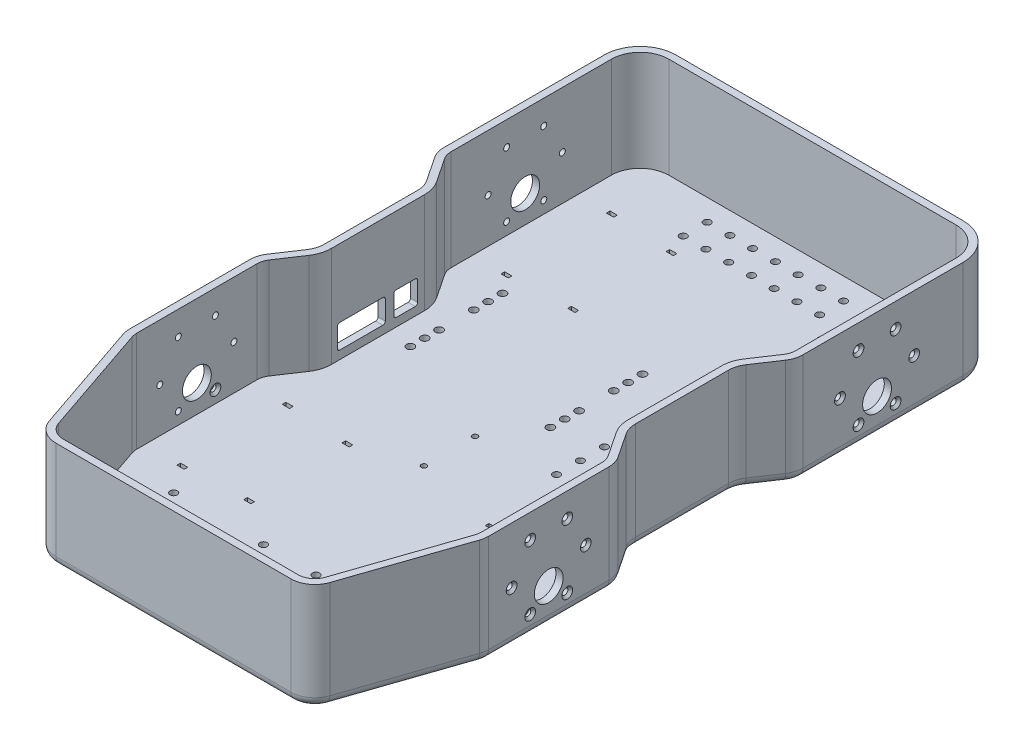
SolidWorks part; units mm, degrees
note: The reader was unsure of these and kept them because the rebuilt part matched: shared geometry of "Sketch13<7>", "Sketch13<15>", "Sketch13<16>".
ref_plane "Front Plane" through (0, 0, 0) normal (0, 0, 1) x (1, 0, 0)
ref_plane "Top Plane" through (0, 0, 0) normal (0, 1, 0) x (1, 0, 0)
ref_plane "Right Plane" through (0, 0, 0) normal (1, 0, 0) x (0, 0, -1)
sketch "Sketch1" plane through (0, 0, 0) normal (0, 1, 0) x (1, 0, 0)
  line L0 (-74.4651, -71.569) -> (-58.5591, -118.2267)
  line L3 (-49.094, -125) -> (49.094, -125)
  line L5 (-73.3205, -12.4808) -> (-66.6795, -2.5192)
  line L6 (-65, 3.0278) -> (-65, 41.9722)
  line L7 (-66.6795, 47.5192) -> (-73.3205, 57.4808)
  line L9 (0, 0) -> (0, 199.7745) construction
  line L10 (74.4651, -71.569) -> (58.5591, -118.2267)
  line L11 (73.3205, -12.4808) -> (66.6795, -2.5192)
  line L12 (65, 3.0278) -> (65, 41.9722)
  line L13 (66.6795, 47.5192) -> (73.3205, 57.4808)
  line L15 (75, -18.0278) -> (75, -68.3423)
  line L16 (-75, -18.0278) -> (-75, -68.3423)
  line L21 (75, 63.0278) -> (75, 130)
  line L22 (60, 145) -> (-60, 145)
  line L23 (-75, 130) -> (-75, 63.0278)
  arc A1 (74.4651, -71.569) -> (75, -68.3423) centre (65, -68.3423) ccw
  arc A2 (58.5591, -118.2267) -> (49.094, -125) centre (49.094, -115) cw
  arc A3 (-49.094, -125) -> (-58.5591, -118.2267) centre (-49.094, -115) cw
  arc A4 (-74.4651, -71.569) -> (-75, -68.3423) centre (-65, -68.3423) cw
  arc A6 (-66.6795, -2.5192) -> (-65, 3.0278) centre (-75, 3.0278) ccw
  arc A7 (-65, 41.9722) -> (-66.6795, 47.5192) centre (-75, 41.9722) ccw
  arc A8 (75, -18.0278) -> (73.3205, -12.4808) centre (65, -18.0278) ccw
  arc A9 (66.6795, -2.5192) -> (65, 3.0278) centre (75, 3.0278) cw
  arc A10 (66.6795, 47.5192) -> (65, 41.9722) centre (75, 41.9722) ccw
  arc A11 (75, 63.0278) -> (73.3205, 57.4808) centre (65, 63.0278) cw
  arc A12 (-73.3205, 57.4808) -> (-75, 63.0278) centre (-65, 63.0278) cw
  arc A13 (-75, 130) -> (-60, 145) centre (-60, 130) cw
  arc A14 (75, 130) -> (60, 145) centre (60, 130) ccw
  arc A15 (-75, -18.0278) -> (-73.3205, -12.4808) centre (-65, -18.0278) cw
  point P24 (75, -70)
  point P27 (56.25, -125)
  point P30 (-56.25, -125)
  point P33 (-75, -70)
  point P36 (-75, -15)
  point P39 (-65, 0)
  point P42 (-65, 45)
  point P45 (75, -15)
  point P48 (65, 0)
  point P51 (65, 45)
  point P54 (75, 70)
  point P57 (-75, 70)
  dimension "D8" = 10
  dimension "D9" = 15
  dimension "D11" = 15
  dimension "D14" = 10
  dimension "D2" = 55
  dimension "D5" = 85
  dimension "D13" = 18.75
  dimension "D16" = 55
  dimension "D3" = 270
  dimension "D4" = 75
  dimension "D6" = 150
  dimension "D7" = 65
extrude "Boss-Extrude1" add sketch "Sketch1" along normal blind 45
shell "Shell1" thickness 3
sketch "Sketch13" plane through (-75, 0, 0) normal (-1, 0, 0) x (0, 0, 1)
  line L0 (35.435, 34.9234) -> (43.185, 21.5) construction
  line L1 (43.185, 21.5) -> (27.685, 21.5) construction
  line L2 (43.185, 21.5) -> (35.435, 8.0766) construction
  line L3 (43.185, 21.5) -> (43.185, 14.4801) construction
  line L4 (18.0278, 0) -> (68.3423, 0)
  line L5 (68.3423, 0) -> (68.3423, 45)
  line L6 (68.3423, 45) -> (18.0278, 45)
  line L7 (18.0278, 45) -> (18.0278, 0)
  line L8 (18.0278, 0) -> (68.3423, 0)
  line L9 (68.3423, 0) -> (68.3423, 45)
  line L10 (68.3423, 45) -> (18.0278, 45)
  line L12 (-18.2522, 98.402) -> (-18.2522, -4.5228) construction
  line L13 (-94, 21.5) -> (-109.5, 21.5) construction
  line L14 (-94, 21.5) -> (-101.75, 8.0766) construction
  line L15 (-101.75, 34.9234) -> (-94, 21.5) construction
  line L16 (-94, 21.5) -> (-94, 14.4801) construction
  line L17 (-94, 21.5) -> (43.185, 21.5) construction
  line L18 (-130, 45) -> (-63.0278, 45) construction
  line L19 (-130, 45) -> (-130, 0) construction
  line L26 (18.0278, 45) -> (18.0278, 0)
  arc A0 (52.185, 8.0803) -> (52.185, 8.075) centre (50.935, 8.0766) cw
  arc A1 (52.185, 8.075) -> (52.185, 8.0803) centre (50.935, 8.0766) cw
  arc A2 (59.935, 21.5037) -> (59.935, 21.4983) centre (58.685, 21.5) cw
  arc A3 (59.935, 21.4983) -> (59.935, 21.5037) centre (58.685, 21.5) cw
  arc A4 (29.274, 33.6957) -> (30.3513, 8.1754) centre (43.185, 21.5) ccw
  arc A5 (30.3513, 8.1754) -> (29.274, 33.6957) centre (43.185, 21.5) ccw
  arc A6 (52.185, 34.9271) -> (52.185, 34.9217) centre (50.935, 34.9234) cw
  arc A7 (52.185, 34.9217) -> (52.185, 34.9271) centre (50.935, 34.9234) cw
  arc A8 (37.3975, 12.8118) -> (37.3802, 16.0874) centre (43.185, 14.4801) ccw
  arc A9 (37.3802, 16.0874) -> (37.3975, 12.8118) centre (43.185, 14.4801) ccw
  arc A12 (34.185, 8.075) -> (34.185, 8.0803) centre (35.435, 8.0766) ccw
  arc A13 (34.185, 8.0803) -> (34.185, 8.075) centre (35.435, 8.0766) ccw
  arc A28 (34.185, 34.9217) -> (34.185, 34.9271) centre (35.435, 34.9234) ccw
  arc A29 (34.185, 34.9271) -> (34.185, 34.9217) centre (35.435, 34.9234) ccw
  arc A32 (26.435, 21.4983) -> (26.435, 21.5037) centre (27.685, 21.5) ccw
  arc A33 (26.435, 21.5037) -> (26.435, 21.4983) centre (27.685, 21.5) ccw
  arc A37 (-100.5, 34.9234) -> (-100.5, 34.9234) centre (-101.75, 34.9234) ccw
  arc A38 (-82.5393, 6.9775) -> (-83.333, 36.615) centre (-94, 21.5) ccw
  arc A40 (-88.6695, 11.6757) -> (-88.6761, 17.2971) centre (-94, 14.4801) ccw
  arc A41 (-108.25, 21.5) -> (-108.25, 21.5) centre (-109.5, 21.5) ccw
  arc A44 (-108.25, 21.5) -> (-108.25, 21.5) centre (-109.5, 21.5) ccw
  arc A45 (-100.5, 34.9234) -> (-100.5, 34.9234) centre (-101.75, 34.9234) ccw construction
  arc A46 (-100.5, 8.0766) -> (-100.5, 8.0766) centre (-101.75, 8.0766) ccw
  arc A47 (-83.333, 36.615) -> (-82.5393, 6.9775) centre (-94, 21.5) ccw
  arc A48 (-88.6761, 17.2971) -> (-88.6695, 11.6757) centre (-94, 14.4801) ccw
  arc A49 (-100.5, 8.0766) -> (-100.5, 8.0766) centre (-101.75, 8.0766) ccw
  arc A50 (-87.5, 8.0766) -> (-87.5, 8.0766) centre (-86.25, 8.0766) cw
  arc A51 (-87.5, 8.0766) -> (-87.5, 8.0766) centre (-86.25, 8.0766) cw
  arc A52 (-79.75, 21.5) -> (-79.75, 21.5) centre (-78.5, 21.5) cw
  arc A53 (-79.75, 21.5) -> (-79.75, 21.5) centre (-78.5, 21.5) cw
  arc A54 (-87.5, 34.9234) -> (-87.5, 34.9234) centre (-86.25, 34.9234) cw
  arc A55 (-87.5, 34.9234) -> (-87.5, 34.9234) centre (-86.25, 34.9234) cw
  circle A56 centre (-101.75, 34.9234) radius 1.25
  circle A57 centre (-86.25, 34.9234) radius 1.25
  circle A58 centre (-78.5, 21.5) radius 1.25
  circle A59 centre (-86.25, 8.0766) radius 1.25
  circle A60 centre (-101.75, 8.0766) radius 1.25
  circle A61 centre (-109.5, 21.5) radius 1.25
  dimension "D11" = 18.5
  dimension "D12" = 6.0232
  dimension "D14" = 1.25
  dimension "D15" = 1.25
  dimension "D16" = 1.25
  dimension "D23" = 18.5
  dimension "D25" = 6.0232
  dimension "D28" = 1.25
  dimension "D30" = 1.25
  dimension "D31" = 1.25
  dimension "D2" = 21.5
  dimension "D3" = 60
  dimension "D4" = 60
  dimension "D5" = 30
  dimension "D6" = 15.5
  dimension "D8" = 15.5
  dimension "D7" = 15.5
  dimension "D13" = 7.0199
  dimension "D17" = 15.5
  dimension "D18" = 60
  dimension "D19" = 15.5
  dimension "D20" = 60
  dimension "D21" = 30
  dimension "D22" = 7.0199
  dimension "D29" = 15.5
  dimension "D9" = 50.3145
  dimension "D10" = 25.1573
  dimension "D24" = 66.9722
  dimension "D26" = 36
extrude "Cut-Extrude1" cut sketch "Sketch13" against normal blind 200 and the other way blind 10 contours A8 A9
extrude "Cut-Extrude2" cut sketch "Sketch13<7>" against normal blind 200 and the other way blind 10 contours A28 A29 | A32 A33 | A12 A13 | A1 A0 | A3 A2 | A7 A6
sketch "Sketch13<7>" plane through (-75, 0, 0) normal (-1, 0, 0) x (0, 0, 1) same geometry as "Sketch13"
chamfer "Chamfer1" distance 1 angle 45 1 edges at (-75, 34.9234, 34.185)
chamfer "Chamfer2" distance 1 angle 45 5 edges at (-72, 8.0766, 34.185) (-75, 8.0766, 49.685) (-75, 21.5, 57.435) (-75, 34.9234, 49.685) (-75, 21.5, 26.435)
chamfer "Chamfer3" distance 1 angle 45 1 edges at (-75, 8.0766, 34.185)
chamfer "Chamfer4" distance 1 angle 45 7 edges at (75, 8.0766, 52.185) (72, 8.0766, 52.185) (75, 8.0766, 36.685) (75, 21.5, 28.935) (75, 34.9234, 36.685) (75, 21.5, 59.935) (75, 34.9234, 52.185)
extrude "Cut-Extrude11" cut sketch "Sketch13<15>" against normal through all contours A59 | A60 | A56 | A61 | A57 | A58
sketch "Sketch13<15>" plane through (-75, 0, 0) normal (-1, 0, 0) x (0, 0, 1) same geometry as "Sketch13"
chamfer "Chamfer5" distance 1 angle 45 12 edges at (75, 34.9234, -100.5) (75, 21.5, -108.25) (75, 8.0766, -100.5) (75, 8.0766, -85) (75, 21.5, -77.25) (75, 34.9234, -85) (-75, 8.0766, -100.5) (-75, 8.0766, -85) (-75, 21.5, -77.25) (-75, 21.5, -108.25) (-75, 34.9234, -100.5) (-75, 34.9234, -85)
extrude "Cut-Extrude12" cut sketch "Sketch13<16>" against normal through all contours A40 A48
sketch "Sketch13<16>" plane through (-75, 0, 0) normal (-1, 0, 0) x (0, 0, 1) same geometry as "Sketch13"
fillet "Fillet1" radius 4 28 edges at (70.6066, 0, -140.6066) (75, 0, -96.5139) (74.5709, 0, -60.1299) (70, 0, -52.5) (65.4291, 0, -44.8701) (65, 0, -22.5) (65.4291, 0, -0.1299) (70, 0, 7.5) (74.5709, 0, 15.1299) (75, 0, 43.185) (74.8654, 0, 69.9777) (66.5121, 0, 94.8979) (54.9134, 0, 123.1323) (0, 0, 125) (-54.9134, 0, 123.1323) (-66.5121, 0, 94.8979) (-74.8654, 0, 69.9777) (-75, 0, 43.185) (-74.5709, 0, 15.1299) (-70, 0, 7.5) (-65.4291, 0, -0.1299) (-65, 0, -22.5) (-65.4291, 0, -44.8701) (-70, 0, -52.5) (-74.5709, 0, -60.1299) (-75, 0, -96.5139) (-70.6066, 0, -140.6066) (0, 0, -145)
sketch "Sketch14" plane through (0, 3, 0) normal (0, 1, 0) x (1, 0, 0)
  line L14 (-72, 130) -> (-72, 63.0278)
  line L15 (-70.8244, 59.1449) -> (-64.1833, 49.1833)
  line L16 (-62, 41.9722) -> (-62, 3.0278)
  line L17 (-64.1833, -4.1833) -> (-70.8244, -14.1449)
  line L18 (-72, -18.0278) -> (-72, -68.3423)
  line L19 (-71.6256, -70.601) -> (-55.7195, -117.2587)
  line L20 (-49.094, -122) -> (49.094, -122)
  line L21 (55.7195, -117.2587) -> (71.6256, -70.601)
  line L22 (72, -68.3423) -> (72, -18.0278)
  line L23 (70.8244, -14.1449) -> (64.1833, -4.1833)
  line L24 (62, 3.0278) -> (62, 41.9722)
  line L25 (64.1833, 49.1833) -> (70.8244, 59.1449)
  line L26 (72, 63.0278) -> (72, 130)
  line L27 (60, 142) -> (-60, 142)
  line L28 (-72, 130) -> (-72, 63.0278)
  line L29 (-70.8244, 59.1449) -> (-64.1833, 49.1833)
  line L30 (-62, 41.9722) -> (-62, 3.0278)
  line L31 (-64.1833, -4.1833) -> (-70.8244, -14.1449)
  line L32 (-72, -18.0278) -> (-72, -68.3423)
  line L33 (-71.6256, -70.601) -> (-55.7195, -117.2587)
  line L34 (-49.094, -122) -> (49.094, -122)
  line L35 (55.7195, -117.2587) -> (71.6256, -70.601)
  line L36 (72, -68.3423) -> (72, -18.0278)
  line L37 (70.8244, -14.1449) -> (64.1833, -4.1833)
  line L38 (62, 3.0278) -> (62, 41.9722)
  line L39 (64.1833, 49.1833) -> (70.8244, 59.1449)
  line L40 (72, 63.0278) -> (72, 130)
  line L41 (60, 142) -> (-60, 142)
  arc A14 (-60, 142) -> (-72, 130) centre (-60, 130) ccw
  arc A15 (-72, 63.0278) -> (-70.8244, 59.1449) centre (-65, 63.0278) ccw
  arc A16 (-62, 41.9722) -> (-64.1833, 49.1833) centre (-75, 41.9722) ccw
  arc A17 (-64.1833, -4.1833) -> (-62, 3.0278) centre (-75, 3.0278) ccw
  arc A18 (-70.8244, -14.1449) -> (-72, -18.0278) centre (-65, -18.0278) ccw
  arc A19 (-72, -68.3423) -> (-71.6256, -70.601) centre (-65, -68.3423) ccw
  arc A20 (-55.7195, -117.2587) -> (-49.094, -122) centre (-49.094, -115) ccw
  arc A21 (49.094, -122) -> (55.7195, -117.2587) centre (49.094, -115) ccw
  arc A22 (71.6256, -70.601) -> (72, -68.3423) centre (65, -68.3423) ccw
  arc A23 (72, -18.0278) -> (70.8244, -14.1449) centre (65, -18.0278) ccw
  arc A24 (62, 3.0278) -> (64.1833, -4.1833) centre (75, 3.0278) ccw
  arc A25 (64.1833, 49.1833) -> (62, 41.9722) centre (75, 41.9722) ccw
  arc A26 (70.8244, 59.1449) -> (72, 63.0278) centre (65, 63.0278) ccw
  arc A27 (72, 130) -> (60, 142) centre (60, 130) ccw
  arc A28 (-60, 142) -> (-72, 130) centre (-60, 130) ccw
  arc A29 (-72, 63.0278) -> (-70.8244, 59.1449) centre (-65, 63.0278) ccw
  arc A30 (-62, 41.9722) -> (-64.1833, 49.1833) centre (-75, 41.9722) ccw
  arc A31 (-64.1833, -4.1833) -> (-62, 3.0278) centre (-75, 3.0278) ccw
  arc A32 (-70.8244, -14.1449) -> (-72, -18.0278) centre (-65, -18.0278) ccw
  arc A33 (-72, -68.3423) -> (-71.6256, -70.601) centre (-65, -68.3423) ccw
  arc A34 (-55.7195, -117.2587) -> (-49.094, -122) centre (-49.094, -115) ccw
  arc A35 (49.094, -122) -> (55.7195, -117.2587) centre (49.094, -115) ccw
  arc A36 (71.6256, -70.601) -> (72, -68.3423) centre (65, -68.3423) ccw
  arc A37 (72, -18.0278) -> (70.8244, -14.1449) centre (65, -18.0278) ccw
  arc A38 (62, 3.0278) -> (64.1833, -4.1833) centre (75, 3.0278) ccw
  arc A39 (64.1833, 49.1833) -> (62, 41.9722) centre (75, 41.9722) ccw
  arc A40 (70.8244, 59.1449) -> (72, 63.0278) centre (65, 63.0278) ccw
  arc A41 (72, 130) -> (60, 142) centre (60, 130) ccw
  dimension "D1" = 0
sketch "Sketch15" plane through (0, 3, 0) normal (0, 1, 0) x (1, 0, 0)
  line L14 (-72, 130) -> (-72, 63.0278)
  line L15 (-70.8244, 59.1449) -> (-64.1833, 49.1833)
  line L16 (-62, 41.9722) -> (-62, 3.0278)
  line L17 (-64.1833, -4.1833) -> (-70.8244, -14.1449)
  line L18 (-72, -18.0278) -> (-72, -68.3423)
  line L19 (-71.6256, -70.601) -> (-55.7195, -117.2587)
  line L20 (-49.094, -122) -> (49.094, -122)
  line L21 (55.7195, -117.2587) -> (71.6256, -70.601)
  line L22 (72, -68.3423) -> (72, -18.0278)
  line L23 (70.8244, -14.1449) -> (64.1833, -4.1833)
  line L24 (62, 3.0278) -> (62, 41.9722)
  line L25 (64.1833, 49.1833) -> (70.8244, 59.1449)
  line L26 (72, 63.0278) -> (72, 130)
  line L27 (60, 142) -> (-60, 142)
  line L28 (-72, 130) -> (-72, 63.0278)
  line L29 (-70.8244, 59.1449) -> (-64.1833, 49.1833)
  line L30 (-62, 41.9722) -> (-62, 3.0278)
  line L31 (-64.1833, -4.1833) -> (-70.8244, -14.1449)
  line L32 (-72, -18.0278) -> (-72, -68.3423)
  line L33 (-71.6256, -70.601) -> (-55.7195, -117.2587)
  line L34 (-49.094, -122) -> (49.094, -122)
  line L35 (55.7195, -117.2587) -> (71.6256, -70.601)
  line L36 (72, -68.3423) -> (72, -18.0278)
  line L37 (70.8244, -14.1449) -> (64.1833, -4.1833)
  line L38 (62, 3.0278) -> (62, 41.9722)
  line L39 (64.1833, 49.1833) -> (70.8244, 59.1449)
  line L40 (72, 63.0278) -> (72, 130)
  line L41 (60, 142) -> (-60, 142)
  arc A14 (-60, 142) -> (-72, 130) centre (-60, 130) ccw
  arc A15 (-72, 63.0278) -> (-70.8244, 59.1449) centre (-65, 63.0278) ccw
  arc A16 (-62, 41.9722) -> (-64.1833, 49.1833) centre (-75, 41.9722) ccw
  arc A17 (-64.1833, -4.1833) -> (-62, 3.0278) centre (-75, 3.0278) ccw
  arc A18 (-70.8244, -14.1449) -> (-72, -18.0278) centre (-65, -18.0278) ccw
  arc A19 (-72, -68.3423) -> (-71.6256, -70.601) centre (-65, -68.3423) ccw
  arc A20 (-55.7195, -117.2587) -> (-49.094, -122) centre (-49.094, -115) ccw
  arc A21 (49.094, -122) -> (55.7195, -117.2587) centre (49.094, -115) ccw
  arc A22 (71.6256, -70.601) -> (72, -68.3423) centre (65, -68.3423) ccw
  arc A23 (72, -18.0278) -> (70.8244, -14.1449) centre (65, -18.0278) ccw
  arc A24 (62, 3.0278) -> (64.1833, -4.1833) centre (75, 3.0278) ccw
  arc A25 (64.1833, 49.1833) -> (62, 41.9722) centre (75, 41.9722) ccw
  arc A26 (70.8244, 59.1449) -> (72, 63.0278) centre (65, 63.0278) ccw
  arc A27 (72, 130) -> (60, 142) centre (60, 130) ccw
  arc A28 (-60, 142) -> (-72, 130) centre (-60, 130) ccw
  arc A29 (-72, 63.0278) -> (-70.8244, 59.1449) centre (-65, 63.0278) ccw
  arc A30 (-62, 41.9722) -> (-64.1833, 49.1833) centre (-75, 41.9722) ccw
  arc A31 (-64.1833, -4.1833) -> (-62, 3.0278) centre (-75, 3.0278) ccw
  arc A32 (-70.8244, -14.1449) -> (-72, -18.0278) centre (-65, -18.0278) ccw
  arc A33 (-72, -68.3423) -> (-71.6256, -70.601) centre (-65, -68.3423) ccw
  arc A34 (-55.7195, -117.2587) -> (-49.094, -122) centre (-49.094, -115) ccw
  arc A35 (49.094, -122) -> (55.7195, -117.2587) centre (49.094, -115) ccw
  arc A36 (71.6256, -70.601) -> (72, -68.3423) centre (65, -68.3423) ccw
  arc A37 (72, -18.0278) -> (70.8244, -14.1449) centre (65, -18.0278) ccw
  arc A38 (62, 3.0278) -> (64.1833, -4.1833) centre (75, 3.0278) ccw
  arc A39 (64.1833, 49.1833) -> (62, 41.9722) centre (75, 41.9722) ccw
  arc A40 (70.8244, 59.1449) -> (72, 63.0278) centre (65, 63.0278) ccw
  arc A41 (72, 130) -> (60, 142) centre (60, 130) ccw
  dimension "D1" = 0
sketch "Sketch16" plane through (0, 0, 0) normal (0, -1, 0) x (1, 0, 0)
  line L14 (-60, -141) -> (60, -141)
  line L15 (71, -130) -> (71, -63.0278)
  line L16 (69.9923, -59.6996) -> (63.3513, -49.738)
  line L17 (61, -41.9722) -> (61, -3.0278)
  line L18 (63.3513, 4.738) -> (69.9923, 14.6996)
  line L19 (71, 18.0278) -> (71, 68.3423)
  line L20 (70.6791, 70.2783) -> (54.773, 116.936)
  line L21 (49.094, 121) -> (-49.094, 121)
  line L22 (-54.773, 116.936) -> (-70.6791, 70.2783)
  line L23 (-71, 68.3423) -> (-71, 18.0278)
  line L24 (-69.9923, 14.6996) -> (-63.3513, 4.738)
  line L25 (-61, -3.0278) -> (-61, -41.9722)
  line L26 (-63.3513, -49.738) -> (-69.9923, -59.6996)
  line L27 (-71, -63.0278) -> (-71, -130)
  line L28 (-60, -141) -> (60, -141)
  line L29 (71, -130) -> (71, -63.0278)
  line L30 (69.9923, -59.6996) -> (63.3513, -49.738)
  line L31 (61, -41.9722) -> (61, -3.0278)
  line L32 (63.3513, 4.738) -> (69.9923, 14.6996)
  line L33 (71, 18.0278) -> (71, 68.3423)
  line L34 (70.6791, 70.2783) -> (54.773, 116.936)
  line L35 (49.094, 121) -> (-49.094, 121)
  line L36 (-54.773, 116.936) -> (-70.6791, 70.2783)
  line L37 (-71, 68.3423) -> (-71, 18.0278)
  line L38 (-69.9923, 14.6996) -> (-63.3513, 4.738)
  line L39 (-61, -3.0278) -> (-61, -41.9722)
  line L40 (-63.3513, -49.738) -> (-69.9923, -59.6996)
  line L41 (-71, -63.0278) -> (-71, -130)
  arc A14 (60, -141) -> (71, -130) centre (60, -130) ccw
  arc A15 (71, -63.0278) -> (69.9923, -59.6996) centre (65, -63.0278) ccw
  arc A16 (61, -41.9722) -> (63.3513, -49.738) centre (75, -41.9722) ccw
  arc A17 (63.3513, 4.738) -> (61, -3.0278) centre (75, -3.0278) ccw
  arc A18 (69.9923, 14.6996) -> (71, 18.0278) centre (65, 18.0278) ccw
  arc A19 (71, 68.3423) -> (70.6791, 70.2783) centre (65, 68.3423) ccw
  arc A20 (54.773, 116.936) -> (49.094, 121) centre (49.094, 115) ccw
  arc A21 (-49.094, 121) -> (-54.773, 116.936) centre (-49.094, 115) ccw
  arc A22 (-70.6791, 70.2783) -> (-71, 68.3423) centre (-65, 68.3423) ccw
  arc A23 (-71, 18.0278) -> (-69.9923, 14.6996) centre (-65, 18.0278) ccw
  arc A24 (-61, -3.0278) -> (-63.3513, 4.738) centre (-75, -3.0278) ccw
  arc A25 (-63.3513, -49.738) -> (-61, -41.9722) centre (-75, -41.9722) ccw
  arc A26 (-69.9923, -59.6996) -> (-71, -63.0278) centre (-65, -63.0278) ccw
  arc A27 (-71, -130) -> (-60, -141) centre (-60, -130) ccw
  arc A28 (60, -141) -> (71, -130) centre (60, -130) ccw
  arc A29 (71, -63.0278) -> (69.9923, -59.6996) centre (65, -63.0278) ccw
  arc A30 (61, -41.9722) -> (63.3513, -49.738) centre (75, -41.9722) ccw
  arc A31 (63.3513, 4.738) -> (61, -3.0278) centre (75, -3.0278) ccw
  arc A32 (69.9923, 14.6996) -> (71, 18.0278) centre (65, 18.0278) ccw
  arc A33 (71, 68.3423) -> (70.6791, 70.2783) centre (65, 68.3423) ccw
  arc A34 (54.773, 116.936) -> (49.094, 121) centre (49.094, 115) ccw
  arc A35 (-49.094, 121) -> (-54.773, 116.936) centre (-49.094, 115) ccw
  arc A36 (-70.6791, 70.2783) -> (-71, 68.3423) centre (-65, 68.3423) ccw
  arc A37 (-71, 18.0278) -> (-69.9923, 14.6996) centre (-65, 18.0278) ccw
  arc A38 (-61, -3.0278) -> (-63.3513, 4.738) centre (-75, -3.0278) ccw
  arc A39 (-63.3513, -49.738) -> (-61, -41.9722) centre (-75, -41.9722) ccw
  arc A40 (-69.9923, -59.6996) -> (-71, -63.0278) centre (-65, -63.0278) ccw
  arc A41 (-71, -130) -> (-60, -141) centre (-60, -130) ccw
  dimension "D1" = 0
sketch "Sketch18" plane through (0, 3, 0) normal (0, 1, 0) x (1, 0, 0)
  line L0 (-72, -68.3423) -> (72, -68.3423) construction
  line L1 (0, -68.3423) -> (0, -58.9421) construction
  line L14 (-72, 130) -> (-72, 63.0278)
  line L15 (-70.8244, 59.1449) -> (-64.1833, 49.1833)
  line L16 (-62, 41.9722) -> (-62, 3.0278)
  line L17 (-64.1833, -4.1833) -> (-70.8244, -14.1449)
  line L18 (-72, -18.0278) -> (-72, -68.3423)
  line L19 (-71.6256, -70.601) -> (-55.7195, -117.2587)
  line L20 (-49.094, -122) -> (49.094, -122)
  line L21 (55.7195, -117.2587) -> (71.6256, -70.601)
  line L22 (72, -68.3423) -> (72, -18.0278)
  line L23 (70.8244, -14.1449) -> (64.1833, -4.1833)
  line L24 (62, 3.0278) -> (62, 41.9722)
  line L25 (64.1833, 49.1833) -> (70.8244, 59.1449)
  line L26 (72, 63.0278) -> (72, 130)
  line L27 (60, 142) -> (-60, 142)
  line L28 (-72, 130) -> (-72, 63.0278)
  line L29 (-70.8244, 59.1449) -> (-64.1833, 49.1833)
  line L30 (-62, 41.9722) -> (-62, 3.0278)
  line L31 (-64.1833, -4.1833) -> (-70.8244, -14.1449)
  line L32 (-72, -18.0278) -> (-72, -68.3423)
  line L33 (-71.6256, -70.601) -> (-55.7195, -117.2587)
  line L34 (-49.094, -122) -> (49.094, -122)
  line L35 (55.7195, -117.2587) -> (71.6256, -70.601)
  line L36 (72, -68.3423) -> (72, -18.0278)
  line L37 (70.8244, -14.1449) -> (64.1833, -4.1833)
  line L38 (62, 3.0278) -> (62, 41.9722)
  line L39 (64.1833, 49.1833) -> (70.8244, 59.1449)
  line L40 (72, 63.0278) -> (72, 130)
  line L41 (60, 142) -> (-60, 142)
  arc A8 (-48.5, -112.3739) -> (-48.5, -115.3739) centre (-48.5, -113.8739) ccw
  arc A9 (-48.5, -115.3739) -> (-48.5, -112.3739) centre (-48.5, -113.8739) ccw
  arc A10 (-11, -112.3739) -> (-11, -115.3739) centre (-11, -113.8739) ccw
  arc A11 (-11, -115.3739) -> (-11, -112.3739) centre (-11, -113.8739) ccw
  arc A12 (-11, -77.8739) -> (-11, -74.8739) centre (-11, -76.3739) ccw
  arc A13 (-11, -74.8739) -> (-11, -77.8739) centre (-11, -76.3739) ccw
  arc A14 (-60, 142) -> (-72, 130) centre (-60, 130) ccw
  arc A15 (-72, 63.0278) -> (-70.8244, 59.1449) centre (-65, 63.0278) ccw
  arc A16 (-62, 41.9722) -> (-64.1833, 49.1833) centre (-75, 41.9722) ccw
  arc A17 (-64.1833, -4.1833) -> (-62, 3.0278) centre (-75, 3.0278) ccw
  arc A18 (-70.8244, -14.1449) -> (-72, -18.0278) centre (-65, -18.0278) ccw
  arc A19 (-72, -68.3423) -> (-71.6256, -70.601) centre (-65, -68.3423) ccw
  arc A20 (-55.7195, -117.2587) -> (-49.094, -122) centre (-49.094, -115) ccw
  arc A21 (49.094, -122) -> (55.7195, -117.2587) centre (49.094, -115) ccw
  arc A22 (71.6256, -70.601) -> (72, -68.3423) centre (65, -68.3423) ccw
  arc A23 (72, -18.0278) -> (70.8244, -14.1449) centre (65, -18.0278) ccw
  arc A24 (62, 3.0278) -> (64.1833, -4.1833) centre (75, 3.0278) ccw
  arc A25 (64.1833, 49.1833) -> (62, 41.9722) centre (75, 41.9722) ccw
  arc A26 (70.8244, 59.1449) -> (72, 63.0278) centre (65, 63.0278) ccw
  arc A27 (72, 130) -> (60, 142) centre (60, 130) ccw
  arc A28 (-60, 142) -> (-72, 130) centre (-60, 130) ccw
  arc A29 (-72, 63.0278) -> (-70.8244, 59.1449) centre (-65, 63.0278) ccw
  arc A30 (-62, 41.9722) -> (-64.1833, 49.1833) centre (-75, 41.9722) ccw
  arc A31 (-64.1833, -4.1833) -> (-62, 3.0278) centre (-75, 3.0278) ccw
  arc A32 (-70.8244, -14.1449) -> (-72, -18.0278) centre (-65, -18.0278) ccw
  arc A33 (-72, -68.3423) -> (-71.6256, -70.601) centre (-65, -68.3423) ccw
  arc A34 (-55.7195, -117.2587) -> (-49.094, -122) centre (-49.094, -115) ccw
  arc A35 (49.094, -122) -> (55.7195, -117.2587) centre (49.094, -115) ccw
  arc A36 (71.6256, -70.601) -> (72, -68.3423) centre (65, -68.3423) ccw
  arc A37 (72, -18.0278) -> (70.8244, -14.1449) centre (65, -18.0278) ccw
  arc A38 (62, 3.0278) -> (64.1833, -4.1833) centre (75, 3.0278) ccw
  arc A39 (64.1833, 49.1833) -> (62, 41.9722) centre (75, 41.9722) ccw
  arc A40 (70.8244, 59.1449) -> (72, 63.0278) centre (65, 63.0278) ccw
  arc A41 (72, 130) -> (60, 142) centre (60, 130) ccw
  arc A42 (-48.5, -74.8739) -> (-48.5, -77.8739) centre (-48.5, -76.3739) ccw
  arc A43 (-48.5, -77.8739) -> (-48.5, -74.8739) centre (-48.5, -76.3739) ccw
  arc A44 (48.5, -115.3739) -> (48.5, -112.3739) centre (48.5, -113.8739) cw
  arc A45 (48.5, -112.3739) -> (48.5, -115.3739) centre (48.5, -113.8739) cw
  arc A46 (11, -115.3739) -> (11, -112.3739) centre (11, -113.8739) cw
  arc A47 (11, -112.3739) -> (11, -115.3739) centre (11, -113.8739) cw
  arc A48 (11, -74.8739) -> (11, -77.8739) centre (11, -76.3739) cw
  arc A49 (11, -77.8739) -> (11, -74.8739) centre (11, -76.3739) cw
  arc A50 (48.5, -77.8739) -> (48.5, -74.8739) centre (48.5, -76.3739) cw
  arc A51 (48.5, -74.8739) -> (48.5, -77.8739) centre (48.5, -76.3739) cw
  dimension "D7" = 1.5
  dimension "D2" = 37.5
  dimension "D3" = 37.5
  dimension "D4" = 8.1261
  dimension "D5" = 37.5
  dimension "D6" = 61
  dimension "D1" = 0
extrude "Cut-Extrude5" cut sketch "Sketch18" against normal through all contours A49 A48 | A51 A50 | A42 A43 | A45 A44 | A47 A46 | A10 A11 | A8 A9 | A13 A12
sketch "Sketch19" plane through (0, 3, 0) normal (0, 1, 0) x (1, 0, 0)
  line L0 (62, 3.0278) -> (62, 41.9722) construction
  line L1 (60, 142) -> (-60, 142) construction
  circle A86 centre (56, -14.34) radius 1.125
  circle A88 centre (-5.98, -14.34) radius 1.125
  circle A90 centre (-5.98, 7) radius 1.125
  circle A92 centre (56, 7) radius 1.125
  dimension "D5" = 2.25
  dimension "D1" = 61.98
  dimension "D2" = 21.34
  dimension "D3" = 6
  dimension "D4" = 135
extrude "Cut-Extrude6" cut sketch "Sketch19" against normal through all contours A90 | A92 | A86 | A88
sketch "Sketch20" plane through (0, 3, 0) normal (0, 1, 0) x (1, 0, 0)
  line L14 (-72, 130) -> (-72, 63.0278)
  line L15 (-70.8244, 59.1449) -> (-64.1833, 49.1833)
  line L16 (-62, 41.9722) -> (-62, 3.0278)
  line L17 (-64.1833, -4.1833) -> (-70.8244, -14.1449)
  line L18 (-72, -18.0278) -> (-72, -68.3423)
  line L19 (-71.6256, -70.601) -> (-55.7195, -117.2587)
  line L20 (-49.094, -122) -> (49.094, -122)
  line L21 (55.7195, -117.2587) -> (71.6256, -70.601)
  line L22 (72, -68.3423) -> (72, -18.0278)
  line L23 (70.8244, -14.1449) -> (64.1833, -4.1833)
  line L24 (62, 3.0278) -> (62, 41.9722)
  line L25 (64.1833, 49.1833) -> (70.8244, 59.1449)
  line L26 (72, 63.0278) -> (72, 130)
  line L27 (60, 142) -> (-60, 142)
  line L28 (-72, 130) -> (-72, 63.0278)
  line L29 (-70.8244, 59.1449) -> (-64.1833, 49.1833)
  line L30 (-62, 41.9722) -> (-62, 3.0278)
  line L31 (-64.1833, -4.1833) -> (-70.8244, -14.1449)
  line L32 (-72, -18.0278) -> (-72, -68.3423)
  line L33 (-71.6256, -70.601) -> (-55.7195, -117.2587)
  line L34 (-49.094, -122) -> (49.094, -122)
  line L35 (55.7195, -117.2587) -> (71.6256, -70.601)
  line L36 (72, -68.3423) -> (72, -18.0278)
  line L37 (70.8244, -14.1449) -> (64.1833, -4.1833)
  line L38 (62, 3.0278) -> (62, 41.9722)
  line L39 (64.1833, 49.1833) -> (70.8244, 59.1449)
  line L40 (72, 63.0278) -> (72, 130)
  line L41 (60, 142) -> (-60, 142)
  arc A14 (-60, 142) -> (-72, 130) centre (-60, 130) ccw
  arc A15 (-72, 63.0278) -> (-70.8244, 59.1449) centre (-65, 63.0278) ccw
  arc A16 (-62, 41.9722) -> (-64.1833, 49.1833) centre (-75, 41.9722) ccw
  arc A17 (-64.1833, -4.1833) -> (-62, 3.0278) centre (-75, 3.0278) ccw
  arc A18 (-70.8244, -14.1449) -> (-72, -18.0278) centre (-65, -18.0278) ccw
  arc A19 (-72, -68.3423) -> (-71.6256, -70.601) centre (-65, -68.3423) ccw
  arc A20 (-55.7195, -117.2587) -> (-49.094, -122) centre (-49.094, -115) ccw
  arc A21 (49.094, -122) -> (55.7195, -117.2587) centre (49.094, -115) ccw
  arc A22 (71.6256, -70.601) -> (72, -68.3423) centre (65, -68.3423) ccw
  arc A23 (72, -18.0278) -> (70.8244, -14.1449) centre (65, -18.0278) ccw
  arc A24 (62, 3.0278) -> (64.1833, -4.1833) centre (75, 3.0278) ccw
  arc A25 (64.1833, 49.1833) -> (62, 41.9722) centre (75, 41.9722) ccw
  arc A26 (70.8244, 59.1449) -> (72, 63.0278) centre (65, 63.0278) ccw
  arc A27 (72, 130) -> (60, 142) centre (60, 130) ccw
  arc A28 (-60, 142) -> (-72, 130) centre (-60, 130) ccw
  arc A29 (-72, 63.0278) -> (-70.8244, 59.1449) centre (-65, 63.0278) ccw
  arc A30 (-62, 41.9722) -> (-64.1833, 49.1833) centre (-75, 41.9722) ccw
  arc A31 (-64.1833, -4.1833) -> (-62, 3.0278) centre (-75, 3.0278) ccw
  arc A32 (-70.8244, -14.1449) -> (-72, -18.0278) centre (-65, -18.0278) ccw
  arc A33 (-72, -68.3423) -> (-71.6256, -70.601) centre (-65, -68.3423) ccw
  arc A34 (-55.7195, -117.2587) -> (-49.094, -122) centre (-49.094, -115) ccw
  arc A35 (49.094, -122) -> (55.7195, -117.2587) centre (49.094, -115) ccw
  arc A36 (71.6256, -70.601) -> (72, -68.3423) centre (65, -68.3423) ccw
  arc A37 (72, -18.0278) -> (70.8244, -14.1449) centre (65, -18.0278) ccw
  arc A38 (62, 3.0278) -> (64.1833, -4.1833) centre (75, 3.0278) ccw
  arc A39 (64.1833, 49.1833) -> (62, 41.9722) centre (75, 41.9722) ccw
  arc A40 (70.8244, 59.1449) -> (72, 63.0278) centre (65, 63.0278) ccw
  arc A41 (72, 130) -> (60, 142) centre (60, 130) ccw
  arc A52 (6.2472, 24.4201) -> (6.7528, 24.4201) centre (6.5, 26) ccw
  arc A53 (6.7528, 24.4201) -> (6.2472, 24.4201) centre (6.5, 26) ccw
  arc A54 (6.2472, 50.9201) -> (6.7528, 50.9201) centre (6.5, 52.5) ccw
  arc A55 (6.7528, 50.9201) -> (6.2472, 50.9201) centre (6.5, 52.5) ccw
  arc A56 (-52.2528, 50.9201) -> (-51.7472, 50.9201) centre (-52, 52.5) ccw
  arc A57 (-51.7472, 50.9201) -> (-52.2528, 50.9201) centre (-52, 52.5) ccw
  arc A58 (-52.2528, 24.4201) -> (-51.7472, 24.4201) centre (-52, 26) ccw
  arc A59 (-51.7472, 24.4201) -> (-52.2528, 24.4201) centre (-52, 26) ccw
  dimension "D6" = 1.6
  dimension "D2" = 58.5
  dimension "D3" = 26.5
  dimension "D4" = 10
  dimension "D5" = 116
  dimension "D1" = 0
extrude "Cut-Extrude7" cut sketch "Sketch20" against normal blind 10 contours A56 A57 | A58 A59 | A54 A55 | A52 A53
sketch "Sketch21" plane through (0, 3, 0) normal (0, 1, 0) x (1, 0, 0)
  line L8 (60, 142) -> (-60, 142) construction
  line L9 (43.8703, 123.4984) -> (57, 123.4984)
  line L10 (43.8703, 123.4984) -> (43.8703, 132)
  line L11 (43.8703, 132) -> (57, 132)
  line L12 (57, 123.4984) -> (57, 132)
  line L13 (72, 63.0278) -> (72, 130) construction
  line L16 (32.0376, 116.2208) -> (32.0376, 114.1208)
  arc A10 (45.0376, 107.9708) -> (45.0876, 108.0208) centre (45.0376, 108.0208) ccw
  dimension "D1" = 13.1297
  dimension "D2" = 8.5016
  dimension "D3" = 10
  dimension "D4" = 15
extrude "Cut-Extrude13" cut sketch "Sketch21" against normal blind 10 contours L9 L12 L11 L10
ref_plane "Plane1" through (-192.3694, 44.6369, -11.8377) normal (0, 1, 0) x (1, 0, 0)
sketch "Sketch24" plane through (-192.3694, 44.6369, -11.8377) normal (0, 1, 0) x (1, 0, 0)
  line L0 (132.3696, 130.1623) -> (144.3693, 130.1623)
  line L1 (138.3694, 130.2075) -> (138.3694, 127.6134) construction
  line L2 (120.3694, 118.1623) -> (120.3694, 51.19) construction
  line L3 (252.3694, 130.1623) -> (132.3694, 130.1623) construction
  line L4 (192.3694, 130.1623) -> (192.3694, 114.7013) construction
  line L5 (252.3693, 130.1623) -> (240.3696, 130.1623)
  line L6 (130.3694, 17.1341) -> (130.3694, 5.1341)
  line L7 (130.3694, 11.1341) -> (133.3694, 11.1341) construction
  line L8 (143.2755, -133.8377) -> (241.4634, -133.8377) construction
  line L9 (130.3694, 30.245) -> (130.3694, -8.5559) construction
  line L10 (130.2722, 30.1341) -> (134.4415, 30.1341) construction
  line L11 (254.3694, 17.1341) -> (254.3694, 5.1341)
  line L12 (198.3226, -133.8377) -> (186.3226, -133.8377)
  line L15 (192.3226, -131.4888) -> (192.3226, -133.8377) construction
  arc A0 (132.3696, 130.1623) -> (144.3693, 130.1623) centre (138.3694, 130.2075) ccw
  circle A1 centre (138.3694, 127.1623) radius 1.5
  circle A2 centre (246.3694, 127.1623) radius 1.5
  arc A3 (252.3693, 130.1623) -> (240.3696, 130.1623) centre (246.3694, 130.2075) cw
  arc A5 (130.3694, 5.1341) -> (130.3694, 17.1341) centre (130.3694, 11.1341) ccw
  circle A6 centre (133.3694, 11.1341) radius 1.5
  circle A7 centre (251.3694, 11.1341) radius 1.5
  arc A8 (254.3694, 5.1341) -> (254.3694, 17.1341) centre (254.3694, 11.1341) cw
  arc A9 (198.3226, -133.8377) -> (186.3226, -133.8377) centre (192.3226, -133.8377) ccw
  circle A10 centre (192.3226, -131.4888) radius 1.5514
  dimension "D1" = 18
  dimension "D2" = 6
  dimension "D3" = 3
  dimension "D6" = 12
  dimension "D7" = 6
  dimension "D8" = 0
  dimension "D15" = 6
  dimension "D16" = 3.1027
  dimension "D4" = 3
  dimension "D5" = 0
  dimension "D9" = 38.8008
  dimension "D10" = 19
  dimension "D11" = 3
  dimension "D12" = 0
  dimension "D14" = 12
sketch "Sketch25" plane through (0, 3, 0) normal (0, 1, 0) x (1, 0, 0)
  line L0 (15.9476, 94) -> (10.8154, 94) construction
  line L1 (56.3327, 116.7507) -> (59.3327, 116.7507)
  line L2 (56.3327, 116.7507) -> (56.3327, 115.2507)
  line L3 (56.3327, 115.2507) -> (59.3327, 115.2507)
  line L4 (59.3327, 116.7507) -> (59.3327, 115.2507)
  line L5 (29.9219, 115.2967) -> (32.9219, 115.2967)
  line L6 (29.9219, 115.2967) -> (29.9219, 113.7967)
  line L7 (29.9219, 113.7967) -> (32.9219, 113.7967)
  line L8 (32.9219, 115.2967) -> (32.9219, 113.7967)
  line L9 (56.3327, 72.7493) -> (59.3327, 72.7493)
  line L10 (59.3327, 71.2493) -> (59.3327, 72.7493)
  line L11 (56.3327, 71.2493) -> (59.3327, 71.2493)
  line L12 (56.3327, 71.2493) -> (56.3327, 72.7493)
  line L13 (29.9219, 74.2033) -> (32.9219, 74.2033)
  line L14 (32.9219, 72.7033) -> (32.9219, 74.2033)
  line L15 (29.9219, 72.7033) -> (32.9219, 72.7033)
  line L16 (29.9219, 72.7033) -> (29.9219, 74.2033)
  line L17 (0, 128.6305) -> (0, 117.335) construction
  line L18 (-56.3327, 71.2493) -> (-56.3327, 72.7493)
  line L19 (-56.3327, 71.2493) -> (-59.3327, 71.2493)
  line L20 (-59.3327, 71.2493) -> (-59.3327, 72.7493)
  line L21 (-56.3327, 72.7493) -> (-59.3327, 72.7493)
  line L22 (-29.9219, 72.7033) -> (-29.9219, 74.2033)
  line L23 (-29.9219, 72.7033) -> (-32.9219, 72.7033)
  line L24 (-32.9219, 72.7033) -> (-32.9219, 74.2033)
  line L25 (-29.9219, 74.2033) -> (-32.9219, 74.2033)
  line L26 (-56.3327, 115.2507) -> (-59.3327, 115.2507)
  line L27 (-59.3327, 116.7507) -> (-59.3327, 115.2507)
  line L28 (-56.3327, 116.7507) -> (-59.3327, 116.7507)
  line L29 (-56.3327, 116.7507) -> (-56.3327, 115.2507)
  line L30 (-29.9219, 113.7967) -> (-32.9219, 113.7967)
  line L31 (-32.9219, 115.2967) -> (-32.9219, 113.7967)
  line L32 (-29.9219, 115.2967) -> (-32.9219, 115.2967)
  line L33 (-29.9219, 115.2967) -> (-29.9219, 113.7967)
  line L34 (28.4219, -21.6229) -> (31.4219, -21.6229)
  line L35 (54.8327, -20.1689) -> (54.8327, -21.6689)
  line L36 (31.4219, -64.2162) -> (31.4219, -62.7162)
  line L37 (54.8327, -65.6703) -> (57.8327, -65.6703)
  line L38 (28.4219, -23.1229) -> (31.4219, -23.1229)
  line L39 (28.4219, -62.7162) -> (31.4219, -62.7162)
  line L40 (54.8327, -65.6703) -> (54.8327, -64.1703)
  line L41 (28.4219, -21.6229) -> (28.4219, -23.1229)
  line L42 (57.8327, -20.1689) -> (57.8327, -21.6689)
  line L43 (57.8327, -65.6703) -> (57.8327, -64.1703)
  line L44 (54.8327, -21.6689) -> (57.8327, -21.6689)
  line L45 (31.4219, -21.6229) -> (31.4219, -23.1229)
  line L46 (28.4219, -64.2162) -> (31.4219, -64.2162)
  line L47 (28.4219, -64.2162) -> (28.4219, -62.7162)
  line L48 (54.8327, -20.1689) -> (57.8327, -20.1689)
  line L49 (54.8327, -64.1703) -> (57.8327, -64.1703)
  line L50 (-28.4219, -64.2162) -> (-31.4219, -64.2162)
  line L51 (-28.4219, -64.2162) -> (-28.4219, -62.7162)
  line L52 (-28.4219, -62.7162) -> (-31.4219, -62.7162)
  line L53 (-31.4219, -64.2162) -> (-31.4219, -62.7162)
  line L54 (-54.8327, -65.6703) -> (-54.8327, -64.1703)
  line L55 (-54.8327, -65.6703) -> (-57.8327, -65.6703)
  line L56 (-57.8327, -65.6703) -> (-57.8327, -64.1703)
  line L57 (-54.8327, -64.1703) -> (-57.8327, -64.1703)
  line L58 (-54.8327, -20.1689) -> (-57.8327, -20.1689)
  line L59 (-57.8327, -20.1689) -> (-57.8327, -21.6689)
  line L60 (-54.8327, -21.6689) -> (-57.8327, -21.6689)
  line L61 (-54.8327, -20.1689) -> (-54.8327, -21.6689)
  line L62 (-28.4219, -21.6229) -> (-28.4219, -23.1229)
  line L63 (-28.4219, -23.1229) -> (-31.4219, -23.1229)
  line L64 (-31.4219, -21.6229) -> (-31.4219, -23.1229)
  line L65 (-28.4219, -21.6229) -> (-31.4219, -21.6229)
  dimension "D1" = 3
  dimension "D2" = 3
  dimension "D3" = 1.5
  dimension "D4" = 1.5
extrude "Cut-Extrude14" cut sketch "Sketch25" against normal blind 10
sketch "Sketch26" plane through (-65, 0, 0) normal (-1, 0, 0) x (0, 0, 1)
  line L4 (-24.5329, 16.4734) -> (-6.5329, 16.4734)
  line L5 (-5.5329, 15.4734) -> (-5.5329, 7.4734)
  line L6 (-6.5329, 6.4734) -> (-24.5329, 6.4734)
  line L7 (-25.5329, 7.4734) -> (-25.5329, 15.4734)
  line L8 (-38.0941, 16.4734) -> (-30.0941, 16.4734)
  line L9 (-29.0941, 15.4734) -> (-29.0941, 7.4734)
  line L10 (-30.0941, 6.4734) -> (-38.0941, 6.4734)
  line L11 (-39.0941, 7.4734) -> (-39.0941, 15.4734)
  arc A0 (-24.5329, 16.4734) -> (-25.5329, 15.4734) centre (-24.5329, 15.4734) ccw
  arc A1 (-24.5329, 6.4734) -> (-25.5329, 7.4734) centre (-24.5329, 7.4734) cw
  arc A2 (-6.5329, 6.4734) -> (-5.5329, 7.4734) centre (-6.5329, 7.4734) ccw
  arc A3 (-5.5329, 15.4734) -> (-6.5329, 16.4734) centre (-6.5329, 15.4734) ccw
  arc A12 (-39.0941, 7.4734) -> (-38.0941, 6.4734) centre (-38.0941, 7.4734) ccw
  arc A13 (-30.0941, 6.4734) -> (-29.0941, 7.4734) centre (-30.0941, 7.4734) ccw
  arc A14 (-29.0941, 15.4734) -> (-30.0941, 16.4734) centre (-30.0941, 15.4734) ccw
  arc A15 (-39.0941, 15.4734) -> (-38.0941, 16.4734) centre (-38.0941, 15.4734) cw
  point P10 (-39.0941, 6.4734)
  point P15 (-25.5329, 16.4734)
  point P20 (-5.5329, 6.4734)
  point P23 (-5.5329, 16.4734)
  point P26 (-29.0941, 16.4734)
  point P29 (-39.0941, 16.4734)
  dimension "D8" = 1
  dimension "D4" = 1
  dimension "D1" = 10
  dimension "D2" = 10
  dimension "D3" = 20
  dimension "D5" = 10
extrude "Cut-Extrude15" cut sketch "Sketch26" against normal blind 4
sketch "Sketch28" plane through (0, 0, 125) normal (0, 0, 1) x (1, 0, 0)
  line L0 (49.094, 24.5) -> (-49.094, 24.5) construction
  line L1 (49.094, 45) -> (49.094, 4) construction
  line L2 (-49.094, 45) -> (-49.094, 4) construction
  line L3 (0, 4) -> (0, 30.8427) construction
  line L4 (-49.094, 4) -> (49.094, 4) construction
  line L5 (-42.5, 10.5) -> (42.5, 10.5) construction
  line L6 (-42.5, 12) -> (42.5, 12)
  line L7 (-42.5, 9) -> (42.5, 9)
  arc A0 (-42.5, 12) -> (-42.5, 9) centre (-42.5, 10.5) ccw
  arc A1 (42.5, 9) -> (42.5, 12) centre (42.5, 10.5) ccw
  point P12 (0, 10.5)
  point P18 (0, 24.5)
  dimension "D1" = 14
  dimension "D2" = 3
  dimension "D3" = 85
sketch "Sketch30" plane through (0, 0, -145) normal (0, 0, -1) x (-1, 0, 0)
  line L0 (-60, 24.5) -> (60, 24.5) construction
  line L1 (-60, 45) -> (-60, 4) construction
  line L2 (60, 45) -> (60, 4) construction
  line L3 (0, 45) -> (0, 19.8795) construction
  line L4 (-60, 45) -> (60, 45) construction
  line L5 (-50, 10.5) -> (50, 10.5) construction
  line L6 (-50, 12) -> (50, 12)
  line L7 (-50, 9) -> (50, 9)
  arc A0 (-50, 12) -> (-50, 9) centre (-50, 10.5) ccw
  arc A1 (50, 9) -> (50, 12) centre (50, 10.5) ccw
  point P12 (0, 10.5)
  point P18 (0, 24.5)
  dimension "D1" = 14
  dimension "D2" = 3
  dimension "D3" = 100
sketch "Sketch31" plane through (0, 3, 0) normal (0, 1, 0) x (1, 0, 0)
  line L0 (-52, 26) -> (6.5, 26) construction
  line L1 (-52, 52.5) -> (-52, 26) construction
  line L2 (-52, 52.5) -> (6.5, 52.5) construction
  line L3 (6.5, 52.5) -> (6.5, 26) construction
  line L4 (6.5, 58.5) -> (6.5, 52.5) construction
  line L5 (6.5, 32) -> (-52.0344, 32) construction
  line L6 (6.5, 58.5) -> (-52.0043, 58.5) construction
  line L7 (-52.0043, 58.5) -> (-52.0344, 32) construction
  circle A1 centre (6.5, 58.5) radius 1.6
  circle A2 centre (6.5, 32) radius 1.6
  circle A4 centre (-52.0043, 58.5) radius 1.6
  circle A5 centre (-52.0344, 32) radius 1.6
  circle A9 centre (-52, 64.5) radius 1.6
  circle A10 centre (6.5, 38) radius 1.6
  circle A11 centre (6.5, 64.5) radius 1.6
  circle A12 centre (-52, 38) radius 1.6
  dimension "D5" = 3.2
  dimension "D6" = 3.2
  dimension "D7" = 26.5
  dimension "D1" = 26.5
  dimension "D2" = 26.5
  dimension "D3" = 58.5
  dimension "D4" = 6
  dimension "D8" = 26.5
  dimension "D9" = 58.5
  dimension "D10" = 6
extrude "Cut-Extrude20" cut sketch "Sketch31" against normal blind 4
sketch "Sketch32" plane through (0, 3, 0) normal (0, 1, 0) x (1, 0, 0)
  circle A0 centre (24.845, 50.2094) radius 1.5
  circle A3 centre (24.845, 40.2094) radius 1.5
  circle A4 centre (24.845, 30.2094) radius 1.5
  circle A5 centre (24.845, 20.2094) radius 1.5
  circle A6 centre (24.845, 10.2094) radius 1.5
  circle A7 centre (34.845, 50.2094) radius 1.5
  circle A8 centre (34.845, 40.2094) radius 1.5
  circle A9 centre (34.845, 30.2094) radius 1.5
  circle A10 centre (34.845, 20.2094) radius 1.5
  circle A11 centre (34.845, 10.2094) radius 1.5
  circle A12 centre (44.845, 50.2094) radius 1.5
  circle A13 centre (44.845, 40.2094) radius 1.5
  circle A14 centre (44.845, 30.2094) radius 1.5
  circle A15 centre (44.845, 20.2094) radius 1.5
  circle A16 centre (44.845, 10.2094) radius 1.5
  circle A17 centre (-34.9687, 132.9763) radius 1.5
  circle A18 centre (-25.4687, 132.9763) radius 1.5
  circle A19 centre (-15.9687, 132.9763) radius 1.5
  circle A20 centre (-6.4687, 132.9763) radius 1.5
  circle A21 centre (3.0313, 132.9763) radius 1.5
  circle A22 centre (12.5313, 132.9763) radius 1.5
  circle A23 centre (22.0313, 132.9763) radius 1.5
  circle A24 centre (31.5313, 132.9763) radius 1.5
  circle A25 centre (-34.9687, 122.9763) radius 1.5
  circle A26 centre (-25.4687, 122.9763) radius 1.5
  circle A27 centre (-15.9687, 122.9763) radius 1.5
  circle A28 centre (-6.4687, 122.9763) radius 1.5
  circle A29 centre (3.0313, 122.9763) radius 1.5
  circle A30 centre (12.5313, 122.9763) radius 1.5
  circle A31 centre (22.0313, 122.9763) radius 1.5
  circle A32 centre (31.5313, 122.9763) radius 1.5
  dimension "D1" = 3
  dimension "D4" = 3
  dimension "D2" = 5
  dimension "D3" = 3
  dimension "D5" = 8
  dimension "D6" = 2
extrude "Cut-Extrude21" cut sketch "Sketch32" against normal up to next (3 mm away)
equation "\"D13@Sketch1\"=\"D4@Sketch1\"/4"
equation "\"D6@Sketch1\"=\"D4@Sketch1\"*2"
equation "\"D10@Sketch13\"=\"D9@Sketch13\"/2"
equation "\"D2@Sketch25\"=\"D1@Sketch25\""
equation "\"D4@Sketch25\"=\"D3@Sketch25\""
